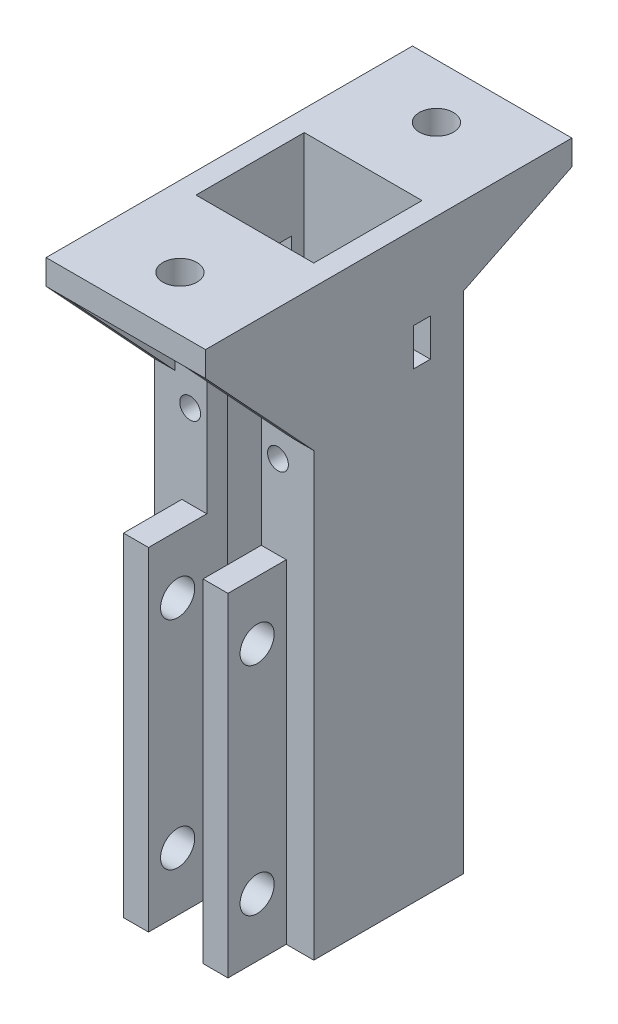
SolidWorks part; units mm, degrees
ref_plane "Front Plane" through (0, 0, 0) normal (0, 0, 1) x (1, 0, 0)
ref_plane "Top Plane" through (0, 0, 0) normal (0, 1, 0) x (1, 0, 0)
ref_plane "Right Plane" through (0, 0, 0) normal (1, 0, 0) x (0, 0, -1)
sketch "Sketch2" plane through (0, 0, 0) normal (0, 1, 0) x (1, 0, 0)
  line L0 (-14.0765, 2.3428) -> (5.0666, 2.3428)
  line L1 (-14.0765, 2.3428) -> (-14.0765, -0.1572)
  line L2 (5.0666, 2.3428) -> (5.0666, -0.1572)
  line L3 (-14.0765, -0.1572) -> (5.0666, -0.1572)
  line L4 (5.0666, 2.3428) -> (5.0666, -13.1572)
  line L5 (5.0666, 2.3428) -> (2.5666, 2.3428)
  line L6 (5.0666, -13.1572) -> (2.5666, -13.1572)
  line L7 (2.5666, 2.3428) -> (2.5666, -13.1572)
  line L8 (-14.0765, 2.3428) -> (-14.0765, -13.1572)
  line L9 (-14.0765, 2.3428) -> (-11.5765, 2.3428)
  line L10 (-14.0765, -13.1572) -> (-11.5765, -13.1572)
  line L11 (-11.5765, 2.3428) -> (-11.5765, -13.1572)
  line L12 (-14.0765, -13.1572) -> (-7.7765, -13.1572)
  line L13 (-14.0765, -13.1572) -> (-14.0765, -15.6572)
  line L14 (-7.7765, -13.1572) -> (-7.7765, -15.6572)
  line L15 (-14.0765, -15.6572) -> (-7.7765, -15.6572)
  line L16 (5.0666, -13.1572) -> (-1.2334, -13.1572)
  line L17 (5.0666, -13.1572) -> (5.0666, -15.6572)
  line L18 (-1.2334, -13.1572) -> (-1.2334, -15.6572)
  line L19 (5.0666, -15.6572) -> (-1.2334, -15.6572)
  line L20 (-7.7765, -15.6572) -> (-10.7765, -15.6572)
  line L21 (-7.7765, -15.6572) -> (-7.7765, -22.6572)
  line L22 (-10.7765, -15.6572) -> (-10.7765, -22.6572)
  line L23 (-7.7765, -22.6572) -> (-10.7765, -22.6572)
  line L24 (-1.2334, -15.6572) -> (1.7666, -15.6572)
  line L25 (-1.2334, -15.6572) -> (-1.2334, -22.6572)
  line L26 (1.7666, -15.6572) -> (1.7666, -22.6572)
  line L27 (-1.2334, -22.6572) -> (1.7666, -22.6572)
  point P0 (-7.9314, -0.1572)
  point P21 (2.5666, -0.1572)
  point P24 (2.5666, -13.1572)
  point P25 (-12.9001, -13.1572)
  dimension "D1" = 0
  dimension "D2" = 2.5
  dimension "D3" = 2.5
  dimension "D4" = 2.5
  dimension "D5" = 6.5431
  dimension "D6" = 360
  dimension "D7" = 13
  dimension "D8" = 2.5
  dimension "D9" = 2.5
  dimension "D10" = 13
  dimension "D11" = 3
  dimension "D12" = 3
  dimension "D13" = 90
  dimension "D14" = 6.3
  dimension "D15" = 6.3
  dimension "D16" = 14.1431
  dimension "D17" = 90
  dimension "D18" = 6.5431
  dimension "D19" = 7
  dimension "D20" = 7
extrude "Boss-Extrude1" add sketch "Sketch2" along normal blind 40 contours L16 L4 L2 L3 L7 | L9 L11 L3 L7 L5 L0 | L8 L12 L11 L3 L1 | L5 L7 L3 L2 | L11 L9 L1 L3 | L13 L15 L14 L12 L11 L10 | L12 L10 L11 | L6 L16 L7 | L19 L17 L6 L7 L16 L18 | L25 L27 L26 L19 | L23 L21 L15 L22 region at (-12.8265, 0, -1.0928) region at (-4.505, 0, -1.0928) region at (-12.8265, 0, 6.6572) region at (3.8166, 0, -1.0928) region at (-10.9265, 0, 14.4072) region at (3.8166, 0, 6.6572) region at (1.9166, 0, 14.4072) region at (-9.2765, 0, 19.1572) region at (0.2666, 0, 19.1572)
sketch "Sketch3" plane through (-10.7765, 0, 0) normal (-1, 0, 0) x (0, 0, 1)
  line L0 (22.6572, 40) -> (22.6572, 0) construction
  line L1 (15.6572, 40) -> (15.6572, 0) construction
  line L2 (15.6572, 40) -> (22.6572, 40) construction
  line L3 (15.6572, 0) -> (22.6572, 0) construction
  circle A0 centre (19.1572, 33) radius 2.05
  circle A1 centre (19.1572, 7) radius 2.05
  dimension "D5" = 4.1
  dimension "D6" = 4.1
  dimension "D1" = 3.5
  dimension "D2" = 3.5
  dimension "D3" = 3.5
  dimension "D4" = 3.5
  dimension "D7" = 7
  dimension "D8" = 7
extrude "Cut-Extrude2" cut sketch "Sketch3" against normal blind 40
sketch "Sketch26" plane through (0, 40, 0) normal (0, 1, 0) x (1, 0, 0)
  line L0 (1.7666, -15.6572) -> (5.0666, -15.6572)
  line L1 (5.0666, -15.6572) -> (5.0666, 2.3428)
  line L2 (5.0666, 2.3428) -> (-14.0765, 2.3428)
  line L3 (-14.0765, 2.3428) -> (-14.0765, -15.6572)
  line L4 (-14.0765, -15.6572) -> (-7.7765, -15.6572)
  line L5 (-7.7765, -13.1572) -> (-7.7765, -22.6572) construction
  line L6 (-7.7765, -15.6572) -> (-7.7765, -13.1572)
  line L7 (-7.7765, -13.1572) -> (-11.5765, -13.1572)
  line L8 (-11.5765, -13.1572) -> (-11.5765, -0.1572)
  line L9 (-11.5765, -0.1572) -> (2.5666, -0.1572)
  line L10 (2.5666, -0.1572) -> (2.5666, -13.1572)
  line L11 (2.5666, -13.1572) -> (-1.2334, -13.1572)
  line L12 (-1.2334, -13.1572) -> (-1.2334, -15.6572)
  line L13 (-1.2334, -13.1572) -> (-1.2334, -22.6572) construction
  line L14 (-1.2334, -15.6572) -> (1.7666, -15.6572)
  line L15 (1.7666, -15.6572) -> (3.6413, -15.6092)
  line M1 (-11.5765, -13.1572) -> (-11.5765, -0.1572)
  line M2 (-11.5765, -0.1572) -> (2.5666, -0.1572)
  line M3 (2.5666, -0.1572) -> (2.5666, -13.1572)
  line M4 (2.5666, -13.1572) -> (-1.2334, -13.1572)
  line M5 (-1.2334, -13.1572) -> (-1.2334, -22.6572)
  line M8 (1.7666, -15.6572) -> (5.0666, -15.6572)
  line M9 (5.0666, -15.6572) -> (5.0666, 2.3428)
  line M10 (5.0666, 2.3428) -> (-14.0765, 2.3428)
  line M11 (-14.0765, 2.3428) -> (-14.0765, -15.6572)
  line M12 (-14.0765, -15.6572) -> (-10.7765, -15.6572)
  line M15 (-7.7765, -22.6572) -> (-7.7765, -13.1572)
  line M16 (-7.7765, -13.1572) -> (-11.5765, -13.1572)
extrude "Boss-Extrude11" add sketch "Sketch26" along normal blind 30 contours L14 L4 M5 M8 M9 M10 M11 M12 M15 M16 M1 M2 M3 M4 region at (0.2666, 40, 15.3945)
sketch "Sketch16" plane through (0, 0, 15.6572) normal (0, 0, 1) x (1, 0, 0)
  line L0 (-7.7765, 70) -> (-7.7765, 40) construction
  line L2 (-14.0765, 70) -> (-7.7765, 70) construction
  circle A0 centre (-9.7765, 50) radius 1.25
  dimension "D1" = 20
  dimension "D2" = 2.5
  dimension "D4" = 2
extrude "Cut-Extrude9" cut sketch "Sketch16" along direction (0, 0, 1) on the side against the normal blind 3.5
sketch "Sketch17" plane through (0, 0, 15.6572) normal (0, 0, 1) x (1, 0, 0)
  line L0 (-1.2334, 70) -> (-1.2334, 40) construction
  line L2 (-1.2334, 70) -> (5.0666, 70) construction
  circle A0 centre (0.7666, 50) radius 1.25
  dimension "D1" = 2.5
  dimension "D2" = 2
  dimension "D3" = 20
extrude "Cut-Extrude10" cut sketch "Sketch17" along direction (0, 0, 1) on the side against the normal blind 3.5
sketch "Sketch18" plane through (0, 0, 13.1572) normal (0, 0, -1) x (-1, 0, 0)
  line L1 (-5.0666, 70) -> (14.0765, 70)
  line L2 (-5.0666, 70) -> (-5.0666, 67)
  line L3 (-5.0666, 67) -> (14.0765, 67)
  line L4 (14.0765, 70) -> (14.0765, 67)
  line L6 (-5.0666, 70) -> (-5.0666, 0) construction
  line L8 (14.0765, 70) -> (7.7765, 70) construction
  dimension "D1" = 0
  dimension "D2" = 0
  dimension "D3" = 3
  dimension "D4" = 0
extrude "Boss-Extrude4" add sketch "Sketch18" against normal blind 15.5
sketch "Sketch19" plane through (0, 0, -2.3428) normal (0, 0, -1) x (-1, 0, 0)
  line L0 (-5.0666, 70) -> (-5.0666, 0) construction
  line L1 (14.0765, 70) -> (-5.0666, 70)
  line L2 (14.0765, 70) -> (14.0765, 67)
  line L3 (14.0765, 67) -> (-5.0666, 67)
  line L4 (-5.0666, 70) -> (-5.0666, 67)
  line L5 (14.0765, 70) -> (14.0765, 0) construction
  dimension "D1" = 3
  dimension "D2" = 0
extrude "Boss-Extrude5" add sketch "Sketch19" along normal blind 13 and the other way blind 2 contours L1 L4 L3 L2
sketch "Sketch21" plane through (-14.0765, 0, 0) normal (-1, 0, 0) x (0, 0, 1)
  line L0 (28.6572, 67) -> (15.6572, 53)
  line L1 (15.6572, 67) -> (15.6572, 0) construction
  line L2 (15.6572, 53) -> (15.6572, 67)
  line L3 (15.6572, 67) -> (28.6572, 67)
  dimension "D1" = 14
extrude "Boss-Extrude6" add sketch "Sketch21" against normal blind 2.5
sketch "Sketch22" plane through (5.0666, 0, 0) normal (1, 0, 0) x (0, 0, -1)
  line L0 (-28.6572, 67) -> (-15.6572, 67)
  line L1 (-15.6572, 67) -> (-15.6572, 53)
  line L2 (-15.6572, 67) -> (-15.6572, 0) construction
  line L3 (-15.6572, 53) -> (-28.6572, 67)
  dimension "D1" = 14
extrude "Boss-Extrude8" add sketch "Sketch22" against normal blind 2.5
sketch "Sketch23" plane through (5.0666, 0, 0) normal (1, 0, 0) x (0, 0, -1)
  line L0 (-13.1572, 70) -> (-13.1572, 53)
  line L2 (15.3428, 70) -> (15.3428, 67)
  line L3 (15.3428, 70) -> (-13.1572, 70)
  line L4 (15.3428, 67) -> (-13.1572, 53)
  dimension "D1" = 28.5
  dimension "D2" = 28.5
  dimension "D3" = 17
  dimension "D4" = 3
  dimension "D5" = 90
extrude "Boss-Extrude9" add sketch "Sketch23" against normal blind 2.5
sketch "Sketch24" plane through (-14.0765, 0, 0) normal (-1, 0, 0) x (0, 0, 1)
  line L0 (13.1572, 70) -> (-15.3428, 70)
  line L1 (-15.3428, 70) -> (-15.3428, 67)
  line L2 (-15.3428, 67) -> (13.1572, 53)
  line L4 (13.1572, 53) -> (13.1572, 70)
  line L5 (-15.3428, 70) -> (-15.3428, 67) construction
  dimension "D1" = 17
  dimension "D2" = 28.5
  dimension "D3" = 3
  dimension "D4" = 90
  dimension "D5" = 0
extrude "Boss-Extrude10" add sketch "Sketch24" against normal blind 2.5
sketch "Sketch25" plane through (0, 70, 0) normal (0, 1, 0) x (1, 0, 0)
  line L0 (-11.5765, 15.3428) -> (-11.5765, 2.3428) construction
  circle A0 centre (-4.705, 8.8428) radius 2.05
  circle A1 centre (-4.505, -22.1572) radius 2.05
  dimension "D1" = 4.1
  dimension "D2" = 4.1
  dimension "D7" = 6.8715
extrude "Cut-Extrude12" cut sketch "Sketch25" against normal blind 3.5
sketch "Sketch27" plane through (5.0666, 0, 0) normal (1, 0, 0) x (0, 0, -1)
  line L0 (-1.6572, 55.5) -> (-1.6572, 60)
  line L1 (-1.6572, 55.5) -> (-3.6572, 55.5)
  line L2 (-1.6572, 60) -> (-3.6572, 60)
  line L3 (-3.6572, 55.5) -> (-3.6572, 60)
  line L4 (-28.6572, 70) -> (15.3428, 70) construction
  line L5 (-0.1572, 70) -> (-0.1572, 0) construction
  dimension "D1" = 4.5
  dimension "D2" = 2
  dimension "D3" = 10
  dimension "D4" = 1.5
extrude "Cut-Extrude13" cut sketch "Sketch27" against normal through all
